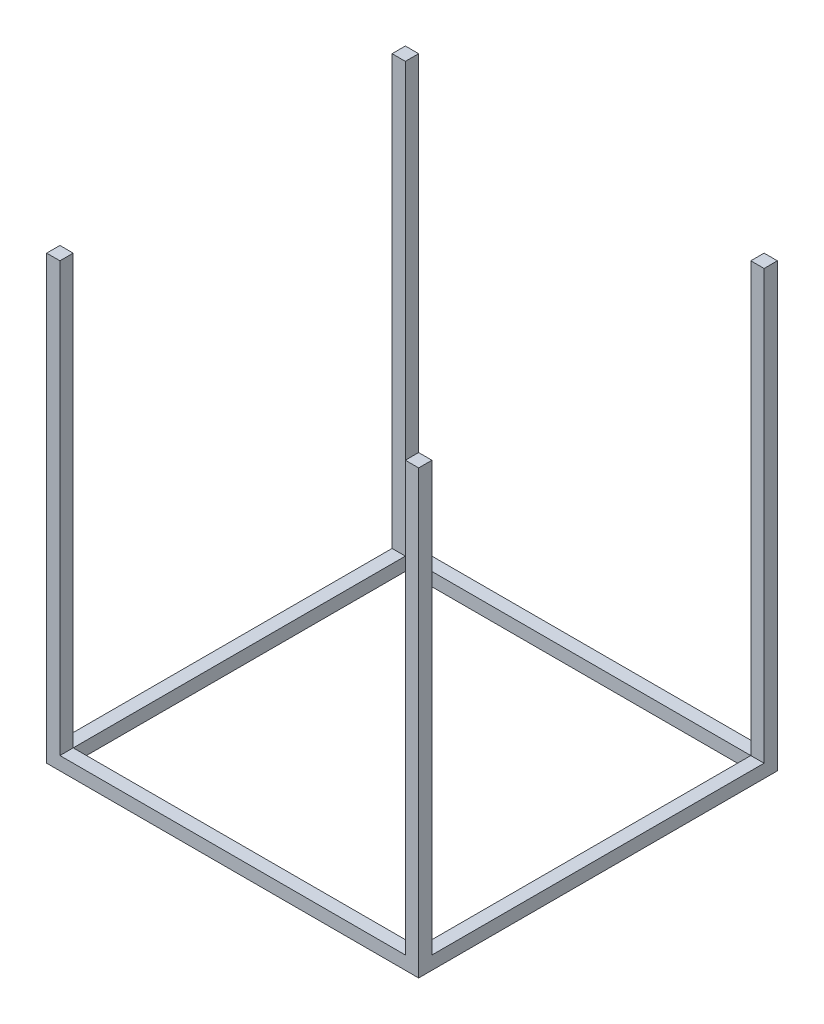
SolidWorks part; units mm, degrees
material "Galvanized Steel"
ref_plane "Front Plane" through (0, 0, 0) normal (0, 0, 1) x (1, 0, 0)
ref_plane "Top Plane" through (0, 0, 0) normal (0, 1, 0) x (1, 0, 0)
ref_plane "Right Plane" through (0, 0, 0) normal (1, 0, 0) x (0, 0, -1)
sketch "Sketch1" plane through (0, 0, 0) normal (0, 1, 0) x (1, 0, 0)
  line L0 (-660.4, 635) -> (-711.2, 635)
  line L1 (-711.2, -685.8) -> (711.2, -685.8)
  line L2 (-711.2, -685.8) -> (-711.2, 685.8)
  line L3 (-711.2, 685.8) -> (711.2, 685.8)
  line L4 (711.2, -685.8) -> (711.2, 685.8)
  line L5 (-711.2, -685.8) -> (711.2, 685.8) construction
  line L6 (-711.2, 685.8) -> (711.2, -685.8) construction
  line L7 (-660.4, -635) -> (660.4, -635)
  line L8 (-660.4, -635) -> (-660.4, 635)
  line L9 (-660.4, 635) -> (660.4, 635)
  line L10 (660.4, -635) -> (660.4, 635)
  line L11 (-660.4, -635) -> (660.4, 635) construction
  line L12 (-660.4, 635) -> (660.4, -635) construction
  line L13 (-660.4, 635) -> (-660.4, 685.8)
  line L14 (660.4, 635) -> (660.4, 685.8)
  line L15 (660.4, 635) -> (711.2, 635)
  line L16 (660.4, -635) -> (711.2, -635)
  line L17 (660.4, -635) -> (660.4, -685.8)
  line L18 (-660.4, -635) -> (-711.2, -635)
  line L19 (-660.4, -635) -> (-660.4, -685.8)
  point P0 (0, 0)
  point P6 (0, 0)
  dimension "D1" = 1320.8
  dimension "D2" = 1270
  dimension "D3" = 50.8
  dimension "D4" = 50.8
extrude "Boss-Extrude1" add sketch "Sketch1" along normal blind 50.8 contours L9 L14 L3 L13 | L18 L8 L0 L2 | L0 L13 L3 L2 | L19 L18 L2 L1 | L7 L19 L1 L17 | L16 L17 L1 L4 | L10 L16 L4 L15 | L14 L15 L4 L3 region at (-685.8, 0, 0) region at (0, 0, -660.4) region at (-685.8, 0, -660.4) region at (-685.8, 0, 660.4) region at (0, 0, 660.4) region at (685.8, 0, 0) region at (685.8, 0, -660.4) region at (685.8, 0, 660.4)
extrude "Boss-Extrude2" add sketch "Sketch1<3>" along normal blind 1689.1 contours L19 L18 L2 L1 | L0 L13 L3 L2 | L14 L15 L4 L3 | L16 L17 L1 L4 region at (-685.8, 0, -660.4) region at (-685.8, 0, 660.4) region at (685.8, 0, -660.4) region at (685.8, 0, 660.4)
sketch "Sketch1<3>" plane through (0, 0, 0) normal (0, 1, 0) x (1, 0, 0) same geometry as "Sketch1"
